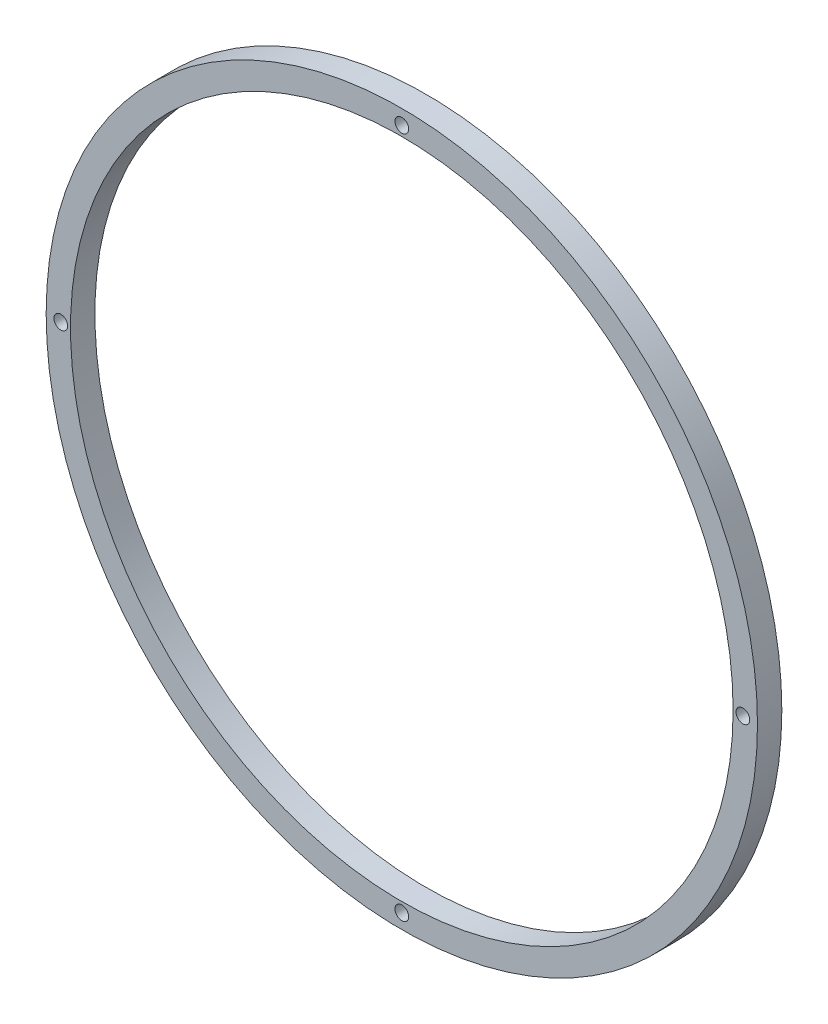
SolidWorks part; units mm, degrees
ref_plane "Front Plane" through (0, 0, 0) normal (0, 0, 1) x (1, 0, 0)
ref_plane "Top Plane" through (0, 0, 0) normal (0, 1, 0) x (1, 0, 0)
ref_plane "Right Plane" through (0, 0, 0) normal (1, 0, 0) x (0, 0, -1)
sketch "Sketch1" plane through (0, 0, 0) normal (0, 0, 1) x (1, 0, 0)
  line L0 (0, 88.9) -> (0, 0) construction
  line L1 (0, 0) -> (-88.9, 0) construction
  circle A0 centre (0, 0) radius 86.36
  circle A1 centre (0, 0) radius 92.71
  circle A2 centre (0, 88.9) radius 1.7859
  circle A3 centre (88.9, 0) radius 1.7859
  circle A4 centre (0, -88.9) radius 1.7859
  circle A5 centre (-88.9, 0) radius 1.7859
  point P15 (0, 0)
  dimension "D1" = 172.72
  dimension "D2" = 185.42
  dimension "D3" = 3.5719
  dimension "D4" = 88.9
  dimension "D6" = 88.9
  dimension "D5" = 4
extrude "Boss-Extrude1" add sketch "Sketch1" along normal blind 6.35 contours A1 A5 A4 A3 A2 A0 region at (-92.4478, 0, 0)
